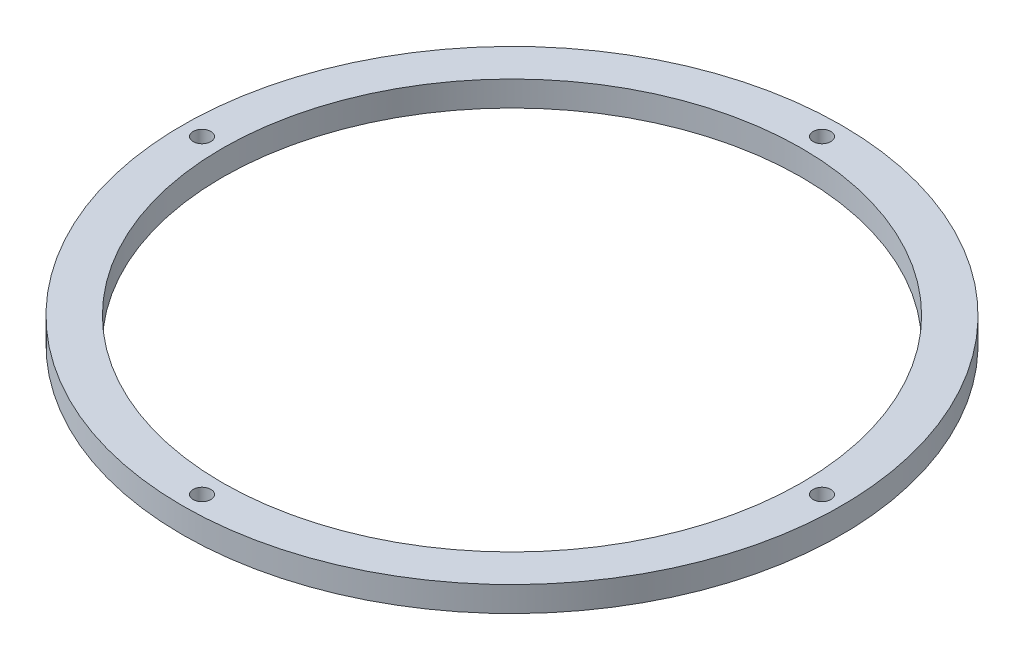
SolidWorks part; units mm, degrees
ref_plane "Front Plane" through (0, 0, 0) normal (0, 0, 1) x (1, 0, 0)
ref_plane "Top Plane" through (0, 0, 0) normal (0, 1, 0) x (1, 0, 0)
ref_plane "Right Plane" through (0, 0, 0) normal (1, 0, 0) x (0, 0, -1)
sketch "Sketch1" plane through (0, 0, 0) normal (0, 1, 0) x (1, 0, 0)
  circle A0 centre (0, 0) radius 111.5
  circle A1 centre (0, 0) radius 98
  dimension "D1" = 223
  dimension "D2" = 196
extrude "Boss-Extrude1" add sketch "Sketch1" along normal blind 8.5
sketch "Sketch2" plane through (0, 8.5, 0) normal (0, 1, 0) x (1, 0, 0)
  circle A0 centre (0, 0) radius 104.875 construction
  circle A1 centre (0, 104.875) radius 3
  circle A2 centre (-104.875, 0) radius 3
  circle A3 centre (104.875, 0) radius 3
  circle A4 centre (0, -104.875) radius 3
  point P12 (0, 0)
  point P13 (0, -89.9211)
  dimension "D1" = 209.75
  dimension "D2" = 6
  dimension "D3" = 6
  dimension "D4" = 6
  dimension "D5" = 6
extrude "Cut-Extrude1" cut sketch "Sketch2" against normal through all contours A1 | A3 | A4 | A2
